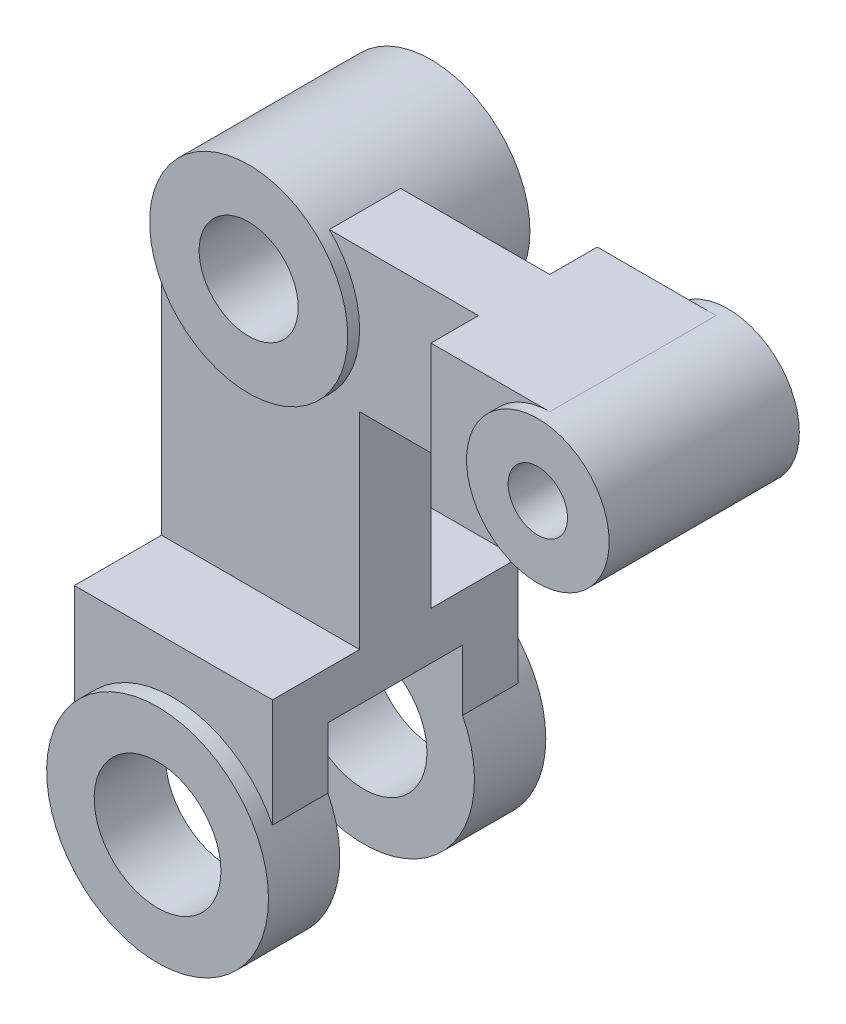
SolidWorks part; units mm, degrees
ref_plane "Front Plane" through (0, 0, 0) normal (0, 0, 1) x (1, 0, 0)
ref_plane "Top Plane" through (0, 0, 0) normal (0, 1, 0) x (1, 0, 0)
ref_plane "Right Plane" through (0, 0, 0) normal (1, 0, 0) x (0, 0, -1)
sketch "Sketch1" plane through (0, 0, 0) normal (0, 0, 1) x (1, 0, 0)
  line L0 (-25, 110) -> (-25, 40)
  line L1 (-25, 40) -> (25, 40)
  line L2 (25, 40) -> (25, 110)
  circle A0 centre (0, 110) radius 25
  circle A1 centre (0, 110) radius 12.5
  dimension "D2" = 50
  dimension "D3" = 25
  dimension "D1" = 110
  dimension "D5" = 40
extrude "Boss-Extrude1" add sketch "Sketch1" along normal blind 3 and the other way blind 43 contours A0 A1 region at (0, 134.2929, 0)
extrude "Boss-Extrude2" add sketch "Sketch1<3>" against normal blind 18 contours A0 L0 L1 L2 region at (0, 65.4916, 0)
sketch "Sketch1<3>" plane through (0, 0, 0) normal (0, 0, 1) x (1, 0, 0) same geometry as "Sketch1"
ref_plane "Plane1" through (0, 0, -9) normal (0, 0, 1) x (1, 0, 0)
sketch "Sketch2" plane through (0, 0, -9) normal (0, 0, 1) x (1, 0, 0)
  line L0 (-25, 40) -> (25, 40) construction
  line L1 (-25, 40) -> (25, 40)
  line L2 (-25, 40) -> (-25, 12.6095)
  line L4 (25, 12.6095) -> (25, 40)
  circle A0 centre (0, 0) radius 28
  circle A1 centre (0, 0) radius 16
  dimension "D1" = 32
  dimension "D2" = 56
extrude "Boss-Extrude3" add sketch "Sketch2" along normal mid plane 70 separate body contours A0 A1 region at (0, 27.208, -9)
extrude "Boss-Extrude4" add sketch "Sketch2<3>" along normal mid plane 62 contours A0 L4 L1 L2 region at (0, 31.2487, -9)
sketch "Sketch2<3>" plane through (0, 0, -9) normal (0, 0, 1) x (1, 0, 0) same geometry as "Sketch2"
sketch "Sketch3" plane through (-25, 0, 0) normal (-1, 0, 0) x (0, 0, 1)
  line L0 (22, 40) -> (22, 12.6095) construction
  line L1 (-26, 28) -> (8, 28)
  line L2 (-26, 28) -> (-26, -55.3802)
  line L3 (-26, -55.3802) -> (8, -55.3802)
  line L4 (8, 28) -> (8, -55.3802)
  line L5 (-40, 28) -> (-40, 12.6095) construction
  line L6 (22, 40) -> (0, 40) construction
  dimension "D1" = 14
  dimension "D2" = 14
  dimension "D3" = 12
extrude "Cut-Extrude1" cut sketch "Sketch3" against normal through all both and the other way through all
sketch "Sketch4" plane through (0, 0, -9) normal (0, 0, 1) x (1, 0, 0)
  line L0 (85, 110) -> (0, 110) construction
  line L1 (85, 128) -> (55, 128)
  line L2 (55, 128) -> (55, 92)
  line L3 (55, 92) -> (85, 92)
  line L4 (55, 128) -> (17.3494, 128)
  line L5 (55, 92) -> (17.3494, 92)
  circle A0 centre (85, 110) radius 18
  circle A1 centre (85, 110) radius 7.5
  circle A2 centre (0, 110) radius 25 construction
  arc A3 (17.3494, 92) -> (17.3494, 128) centre (0, 110) ccw
  point P3 (70, 128)
  dimension "D1" = 36
  dimension "D2" = 15
  dimension "D3" = 85
  dimension "D4" = 15
  dimension "D5" = 30
extrude "Boss-Extrude5" add sketch "Sketch4" along normal mid plane 48 separate body contours A1 A0 region at (97.3679, 122.3679, -9)
extrude "Boss-Extrude6" add sketch "Sketch4<3>" along normal mid plane 42 contours L0 A0 L1 L2 | A0 L0 L2 L3 region at (63.4402, 99.7874, -9) region at (63.4402, 120.2126, -9)
sketch "Sketch4<3>" plane through (0, 0, -9) normal (0, 0, 1) x (1, 0, 0) same geometry as "Sketch4"
extrude "Boss-Extrude7" add sketch "Sketch4<4>" along normal mid plane 18 contours L0 L2 L4 A3 | L2 L0 A3 L5 region at (38.7391, 100.6595, -9) region at (38.7391, 119.3405, -9)
sketch "Sketch4<4>" plane through (0, 0, -9) normal (0, 0, 1) x (1, 0, 0) same geometry as "Sketch4"
